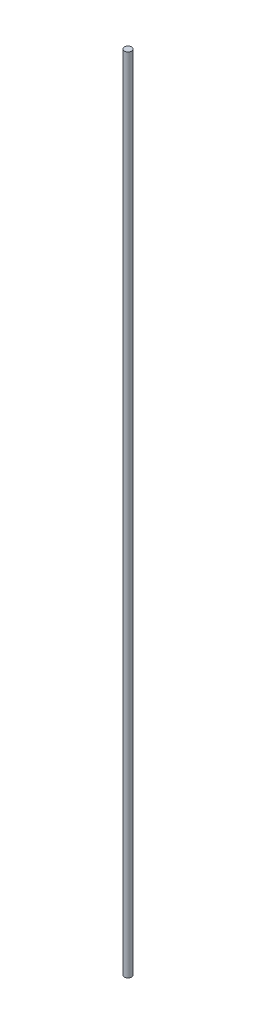
SolidWorks part; units mm, degrees
ref_plane "Спереди" through (0, 0, 0) normal (0, 0, 1) x (1, 0, 0)
ref_plane "Сверху" through (0, 0, 0) normal (0, 1, 0) x (1, 0, 0)
ref_plane "Справа" through (0, 0, 0) normal (1, 0, 0) x (0, 0, -1)
sketch "Эскиз2" plane through (0, 0, 0) normal (0, 0, 1) x (1, 0, 0)
  line L5 (-2.5, 275) -> (0, 275)
  line L6 (-2.5, 275) -> (-2.5, -275)
  line L7 (-2.5, -275) -> (0, -275)
  line L8 (0, 275) -> (0, -275)
  line L9 (-2.5, 275) -> (0, -275) construction
  line L10 (-2.5, -275) -> (0, 275) construction
  point P0 (-1.25, 0)
  point P5 (0, 0)
  dimension "D1" = 2.5
  dimension "D2" = 550
revolve "Повернуть1" add sketch "Эскиз2" angle 360 about L6
equation "\"Ширина груза\"= 420"
equation "\"Глубина груза\"= 490"
equation "\"Высота груза\"= 297"
equation "\"Ширина ячейки\"= \"Ширина груза\" + 10"
equation "\"Глубина ячейки\"= \"Глубина груза\" + 10"
equation "\"Высота ячейки\"= \"Высота груза\" + 10 + 13"
equation "\"Колво ячеек ширина\"= 2"
equation "\"Колво ячеек высота\"= 2"
equation "\"Толщина стенки\" = 6"
equation "\"Крепление дверцы\"= 5"
equation "\"Ширина рейки\"= \"Толщина шестерни\""
equation "\"Высота рейки\"= 20"
equation "\"Высота пола\"= 20"
equation "\"Колво полозьев\"= 5"
equation "\"Отступ рейки\"= 20"
equation "\"Глубина каретки\"= \"Глубина ячейки\" + 30 + \"Мотор Y высота корпуса\" + 20"
equation "\"Длинна рейки\"= ( \"Ширина ячейки\" + \"Толщина стенки\" + \"Крепление дверцы\" ) * \"Колво ячеек ширина\" + \"Ширина ячейки выгрузки\" * \"Колво выгрузки\" + \"Толщина стенки\""
equation "\"Отступ шпильки\"= 26"
equation "\"Диаметр шпильки\"= 5"
equation "\"Длинна шпильки\"= ( \"Высота ячейки\" + \"Толщина стенки\" + \"Высота пола\" ) * \"Колво ячеек высота\" + ( \"Толщина стенки\" + \"Отступ рейки\" ) * 2 "
equation "\"D1@Эскиз2\"= \"Диаметр шпильки\" / 2"
equation "\"D2@Эскиз2\"= \"Глубина каретки\" - \"Мотор Y высота корпуса\""
equation "\"Ширина пластины\"= 50  "
equation "\"Высота зона выгрузки\"= \"Высота ячейки\" * 2 + \"Толщина стенки\" * 2"
equation "\"Колво выгрузки\"= 1"
equation "\"Отступ крепления мотора фиксации\" = 30"
equation "\"Мотор X ширина корпуса\"= 42.3"
equation "\"Мотор X высота корпуса\"= 42.3"
equation "\"Мотор X длина корпуса\"= 40"
equation "\"Мотор X вылет вала\"= 19.8"
equation "\"Мотор Y ширина корпуса\"= 42.3"
equation "\"Мотор Y высота корпуса\"= 42.3"
equation "\"Мотор Y длина корпуса\"= 48"
equation "\"Мотор Y вылет вала\"= 30"
equation "\"Мотор Z ширина корпуса\"= 42"
equation "\"Мотор Z высота корпуса\"= 42"
equation "\"Мотор Z длина корпуса\"= 40"
equation "\"Мотор Z вылет вала\"= 23"
equation "\"Мотор диаметр вала ПРЕДВ\"= 5"
equation "\"Мотор шаг крепления ПРЕДВ\"= 31"
equation "\"Мотор диаметр отверстий ПРЕДВ\"= 3"
equation "\"Мотор глубина отверстий ПРЕДВ\"= 4.5"
equation "\"Мотор диаметр буртика ПРЕДВ\"= 22"
equation "\"Мотор высота буртика ПРЕДВ\"= 2"
equation "\"Мотор диаметр шкива ПРЕДВ\"= 16"
equation "\"Мотор длина шкива ПРЕДВ\"= 12"
equation "\"Мотор отступ шкива ПРЕДВ\"= 5"
equation "\"Мотор X шаг градусов\"= 1.8"
equation "\"Мотор X ток А\"= 1.5"
equation "\"Мотор X сопротивление Ом\"= 1.3"
equation "\"Мотор X индуктивность мГн\"= 2"
equation "\"Мотор Y шаг градусов\"= 1.8"
equation "\"Мотор Y ток А\"= 2.2"
equation "\"Мотор Y сопротивление Ом\"= 0.9"
equation "\"Мотор Y индуктивность мГн\"= 2"
equation "\"Мотор Z шаг градусов\"= 1.8"
equation "\"Мотор Z ток А\"= 1"
equation "\"Мотор Z сопротивление Ом\"= 4"
equation "\"Мотор Z индуктивность мГн\"= 8"
equation "\"Мотор Y диаметр ротора\"= 25.78"
equation "\"Ширина ячейки выгрузки\"= \"Ширина ячейки\" + \"Толщина стенки\" + \"Отступ крепления мотора фиксации\"*2"
